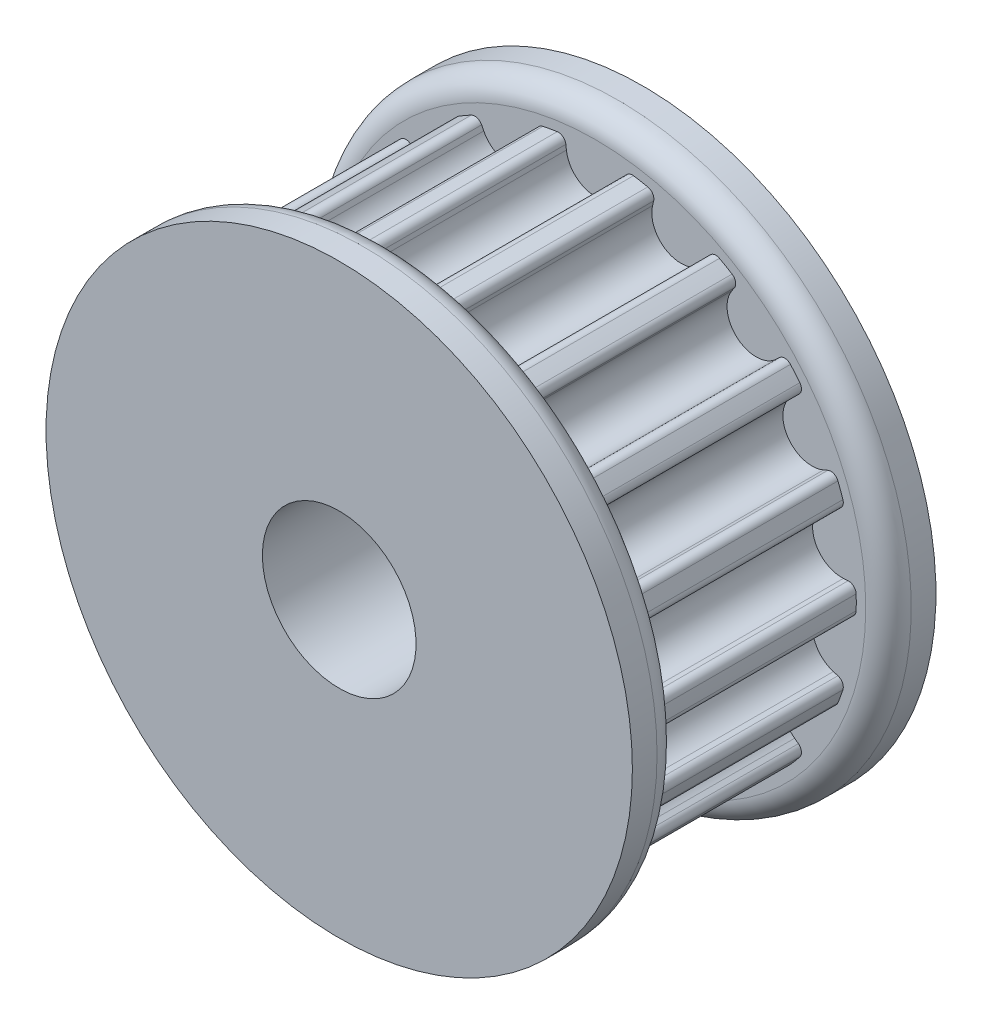
SolidWorks part; units mm, degrees
material "6061 합금"
ref_plane "정면" through (0, 0, 0) normal (0, 0, 1) x (1, 0, 0)
ref_plane "윗면" through (0, 0, 0) normal (0, 1, 0) x (1, 0, 0)
ref_plane "우측면" through (0, 0, 0) normal (1, 0, 0) x (0, 0, -1)
sketch "스케치3" plane through (0, 0, 0) normal (0, 0, 1) x (1, 0, 0)
  line L0 (0, 0) -> (0, 13.7524) construction
  line L1 (0, 0) -> (-4.8991, 13.4601) construction
  line L2 (0, 13.7524) -> (0, 15.4524) construction
  line L3 (-1.5246, 13.0088) -> (-1.6008, 13.659)
  line L4 (1.5246, 13.0088) -> (1.6008, 13.659)
  circle A0 centre (0, 0) radius 14.3239 construction
  circle A1 centre (0, 0) radius 15.4524 construction
  circle A2 centre (0, 0) radius 13.7524
  circle A3 centre (0, 13.1874) radius 1.535
  dimension "D2" = 28.6479
  dimension "D5" = 3.07
  dimension "D3" = 27.5049
  dimension "D1" = 20
  dimension "D4" = 2.1
  dimension "D6" = 3.8
extrude "보스-돌출2" add sketch "스케치3" along normal mid plane 11 contours A2
extrude "컷-돌출2" cut sketch "스케치3<3>" against normal through all both and the other way through all contours A3 A2 L3 | A2 A3 | A3 L4 A2 region at (0, 12.8159, 0) region at (-1.5387, 13.5029, 0) region at (1.5387, 13.5029, 0)
sketch "스케치3<3>" plane through (0, 0, 0) normal (0, 0, 1) x (1, 0, 0) same geometry as "스케치3"
fillet "필렛1" radius 0.4 2 edges at (1.6008, 13.659, 0) (-1.6008, 13.659, 0)
pattern_circular "원형 패턴1" count 18 over 360 about axis through (0, 0, 5.5) along (0, 0, -1) of "컷-돌출2", "필렛1"
sketch "스케치12" plane through (0, 0, 5.5) normal (0, 0, 1) x (1, 0, 0)
  circle A0 centre (0, 0) radius 15.4524 construction
  circle A1 centre (0, 0) radius 15.4524
extrude "보스-돌출4" add sketch "스케치12" along normal blind 2.5
sketch "스케치13" plane through (0, 0, -5.5) normal (0, 0, -1) x (-1, 0, 0)
  circle A0 centre (0, 0) radius 15.4524 construction
  circle A1 centre (0, 0) radius 15.4524
extrude "보스-돌출5" add sketch "스케치13" along normal blind 2.5
fillet "필렛2" radius 1.2 2 edges at (15.4524, 0, 5.5) (-15.4524, 0, -5.5)
sketch "스케치5" plane through (0, 0, -8) normal (0, 0, -1) x (-1, 0, 0)
  circle A2 centre (0, 0) radius 9
  dimension "D1" = 18
extrude "보스-돌출3" add sketch "스케치5" along normal blind 3
sketch "스케치4" plane through (0, 0, 8) normal (0, 0, -1) x (-1, 0, 0)
  circle A0 centre (0, 0) radius 4.05
  dimension "D1" = 8.1
extrude "컷-돌출3" cut sketch "스케치4" along normal through all
hole_wizard "M3x0.5 탭을 위한 탭 드릴1" positions "스케치7" profile "스케치8" hole size "M3x0.5" standard "Ansi Metric" end condition through all
sketch "스케치7" plane through (0, 0, 0) normal (0, 1, 0) x (1, 0, 0)
  line L0 (0, 11) -> (0, 8) construction
  line L1 (9, 11) -> (-9, 11) construction
  line L4 (9, 8) -> (-9, 8) construction
  point P0 (0, 9.5)
sketch "스케치8" plane through (0, 0, -9.5) normal (1, 0, 0) x (0, 0, -1)
  line L0 (0, 0) -> (0, 15.4524)
  line L1 (0, 15.4524) -> (1.2, 15.4524)
  line L2 (1.2, 15.4524) -> (1.2, 0)
  line L5 (1.2, 0) -> (0, 0)
  line L11 (0, -6.35) -> (0, 107.95) construction
  dimension "관통 구멍 지름" = 2.4
  dimension "관통 구멍 깊이" = 15.4524
sketch "스케치14" plane through (0, 0, 8) normal (0, 0, 1) x (1, 0, 0)
  circle A0 centre (0, 0) radius 16
  circle A1 centre (0, 0) radius 18.5
  dimension "D1" = 2.5
  dimension "D2" = 32
extrude "보스-돌출6" [suppressed] add sketch "스케치14" against normal up to surface (13 mm away) separate body
equation "\"n\"= 18'number of teeth"
equation "\"D2@스케치3\"=5*\"n\"/(PI)"
equation "\"D1@스케치3\"=360/\"n\""
equation "\"D1@원형 패턴1\"=\"n\""
equation "\"D3@스케치3\"=\"D2@스케치3\"-2*0.225*2.54"
